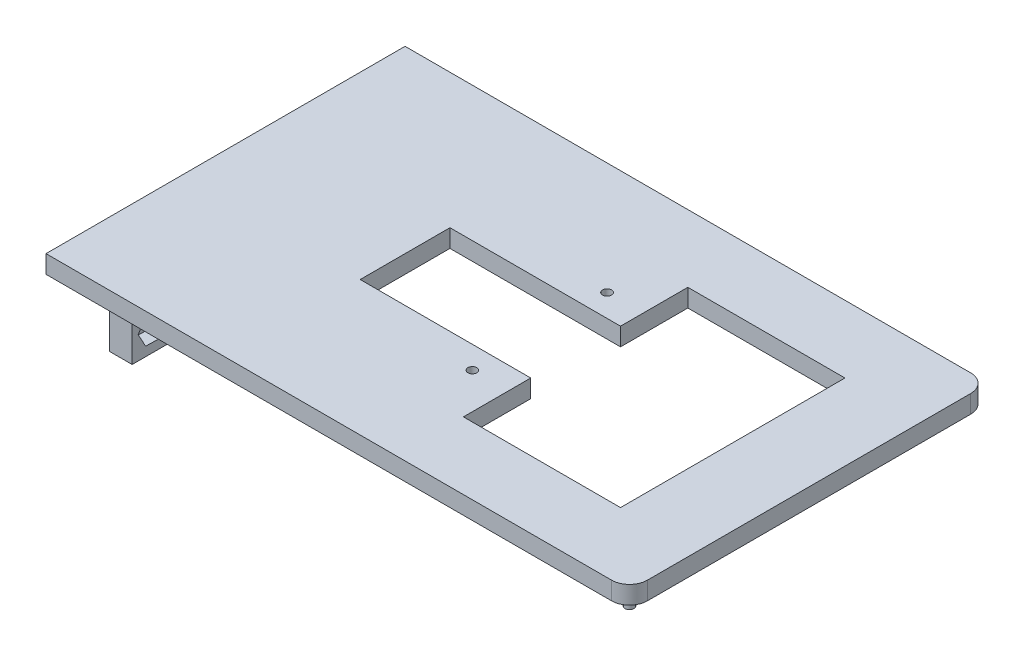
SolidWorks part; units mm, degrees
ref_plane "Front Plane" through (0, 0, 0) normal (0, 0, 1) x (1, 0, 0)
ref_plane "Top Plane" through (0, 0, 0) normal (0, 1, 0) x (1, 0, 0)
ref_plane "Right Plane" through (0, 0, 0) normal (1, 0, 0) x (0, 0, -1)
sketch "Sketch1" plane through (0, 0, 0) normal (0, 1, 0) x (1, 0, 0)
  line L1 (0, 0) -> (130, 0)
  line L2 (0, 0) -> (0, 80)
  line L3 (0, 80) -> (130, 80)
  line L4 (130, 0) -> (130, 80)
  arc A0 (126, 80) -> (130, 76) centre (126, 76) cw
  arc A1 (130, 4) -> (126, 0) centre (126, 4) cw
  point P5 (126, 4)
  point P6 (126, 76)
  dimension "D7" = 4
  dimension "D8" = 4
  dimension "D1" = 80
  dimension "D2" = 130
  dimension "D3" = 4
  dimension "D4" = 4
  dimension "D5" = 4
  dimension "D6" = 4
extrude "Boss-Extrude1" add sketch "Sketch1" along normal blind 4 contours A1 L4 A0 L3 L2 L1 region at (64.9576, 0, -40)
sketch "Sketch2" plane through (0, 0, 0) normal (0, -1, 0) x (-1, 0, 0)
  line L0 (-130, 4) -> (-130, 76) construction
  line L1 (0, 80) -> (-126, 80) construction
  circle A0 centre (-125.5, 4.5) radius 1
  circle A1 centre (-125.5, 75.5) radius 1
  point P0 (-125.5, 4.5)
  dimension "D3" = 2
  dimension "D6" = 2
  dimension "D1" = 4.5
  dimension "D2" = 4.5
  dimension "D4" = 4.5
  dimension "D5" = 4.5
extrude "Boss-Extrude2" add sketch "Sketch2" along normal blind 3.5
sketch "Sketch3" plane through (0, 0, 0) normal (0, -1, 0) x (-1, 0, 0)
  line L0 (0, 0) -> (0, 80) construction
  line L1 (0, 0) -> (-126, 0) construction
  line L2 (0, 80) -> (-126, 80) construction
  line L4 (-12, 2.2) -> (-17, 2.2)
  line L5 (-12, 2.2) -> (-12, 12.2)
  line L6 (-12, 12.2) -> (-17, 12.2)
  line L7 (-17, 2.2) -> (-17, 12.2)
  line L8 (-12, 77.8) -> (-17, 77.8)
  line L9 (-12, 77.8) -> (-12, 67.8)
  line L10 (-12, 67.8) -> (-17, 67.8)
  line L11 (-17, 77.8) -> (-17, 67.8)
  point P0 (-12, 2.2)
  point P1 (-12, 77.8)
  dimension "D1" = 12
  dimension "D2" = 2.2
  dimension "D3" = 2.2
  dimension "D4" = 12
  dimension "D5" = 10
  dimension "D6" = 5
  dimension "D7" = 10
  dimension "D8" = 5
extrude "Boss-Extrude3" add sketch "Sketch3" along normal blind 10
sketch "Sketch4" plane through (17, 0, 0) normal (1, 0, 0) x (0, 0, -1)
  line L0 (12.2, -10) -> (2.2, -10) construction
  line L1 (8.6657, -8.0383) -> (10.4641, -5.0766)
  line L2 (10.4641, -5.0766) -> (8.7984, -2.0383)
  line L3 (8.7984, -2.0383) -> (5.3343, -1.9617)
  line L4 (5.3343, -1.9617) -> (3.5359, -4.9234)
  line L5 (3.5359, -4.9234) -> (5.2016, -7.9617)
  line L6 (5.2016, -7.9617) -> (8.6657, -8.0383)
  line L7 (12.2, -10) -> (12.2, 0) construction
  circle A0 centre (7, -5) radius 3.0007 construction
  circle A1 centre (7, -5) radius 1.55
  dimension "D5" = 3.1
  dimension "D1" = 5
  dimension "D2" = 5.2
  dimension "D3" = 6
  dimension "D4" = 6.0015
extrude "Cut-Extrude1" cut sketch "Sketch4" against normal blind 3 contours L5 L6 L1 L2 L3 L4 A1 region at (17, -7.9079, -6.9357)
sketch "Sketch5" plane through (17, 0, 0) normal (1, 0, 0) x (0, 0, -1)
extrude "Cut-Extrude2" cut sketch "Sketch4<3>" against normal up to surface (5 mm away) contours A1 region at (17, -5, -7) up to face at (12, -5, -7.2)
sketch "Sketch4<3>" plane through (17, 0, 0) normal (1, 0, 0) x (0, 0, -1) same geometry as "Sketch4"
sketch "Sketch6" plane through (17, 0, 0) normal (1, 0, 0) x (0, 0, -1)
  line L0 (77.8, -10) -> (67.8, -10) construction
  line L1 (71.2679, -2) -> (69.5359, -5)
  line L2 (69.5359, -5) -> (71.2679, -8)
  line L3 (71.2679, -8) -> (74.7321, -8)
  line L4 (74.7321, -8) -> (76.4641, -5)
  line L5 (76.4641, -5) -> (74.7321, -2)
  line L6 (74.7321, -2) -> (71.2679, -2)
  line L7 (67.8, -10) -> (67.8, 0) construction
  circle A0 centre (73, -5) radius 3 construction
  circle A1 centre (73, -5) radius 1.55
  dimension "D5" = 3.1
  dimension "D1" = 6
  dimension "D2" = 6
  dimension "D3" = 5
  dimension "D4" = 5.2
sketch "Sketch7" plane through (0, 0, 0) normal (0, -1, 0) x (1, 0, 0)
  line L0 (0, 0) -> (126, 0) construction
  line L1 (0, 0) -> (0, -80) construction
  circle A0 centre (70, -25) radius 3
  circle A1 centre (70, -55) radius 3
  dimension "D3" = 6
  dimension "D4" = 6
  dimension "D1" = 30
  dimension "D2" = 25
  dimension "D5" = 70
  dimension "D6" = 70
extrude "Cut-Extrude3" cut sketch "Sketch7" against normal blind 2
sketch "Sketch8" plane through (0, 2, 0) normal (0, -1, 0) x (-1, 0, 0)
  line L0 (0, 80) -> (-126, 80) construction
  line L1 (0, 0) -> (0, 80) construction
  circle A0 centre (-70, 55) radius 1
  dimension "D1" = 2
  dimension "D2" = 25
  dimension "D3" = 70
extrude "Cut-Extrude4" cut sketch "Sketch8" against normal blind 2
sketch "Sketch9" plane through (0, 2, 0) normal (0, -1, 0) x (-1, 0, 0)
  line L0 (0, 0) -> (-126, 0) construction
  line L1 (0, 0) -> (0, 80) construction
  circle A0 centre (-70, 25) radius 1
  dimension "D1" = 2
  dimension "D2" = 25
  dimension "D3" = 70
extrude "Cut-Extrude5" cut sketch "Sketch9" against normal blind 2
sketch "Sketch10" plane through (0, 0, 0) normal (0, -1, 0) x (-1, 0, 0)
  line L0 (0, 0) -> (-126, 0) construction
  line L1 (-78, 30) -> (-40, 30)
  line L2 (0, 0) -> (0, 80) construction
  line L3 (-78, 50) -> (-40, 50)
  line L4 (-40, 30) -> (-40, 50)
  line L5 (-130, 4) -> (-130, 76) construction
  line L6 (-78, 30) -> (-78, 15)
  line L7 (-78, 15) -> (-113, 15)
  line L8 (-113, 15) -> (-113, 65)
  line L9 (-113, 65) -> (-78, 65)
  line L10 (-78, 65) -> (-78, 50)
  dimension "D1" = 20
  dimension "D2" = 40
  dimension "D3" = 30
  dimension "D4" = 52
  dimension "D5" = 15
  dimension "D6" = 15
  dimension "D7" = 35
  dimension "D8" = 17
extrude "Cut-Extrude6" cut sketch "Sketch10" against normal blind 4
extrude "Cut-Extrude7" cut sketch "Sketch6" against normal blind 3 contours L5 L6 L1 L2 L3 L4 A1 region at (17, -2.0917, -73)
extrude "Cut-Extrude8" cut sketch "Sketch6<3>" against normal up to surface (5 mm away) contours A1 region at (17, -5, -73) up to face at (12, -5, -72.8)
sketch "Sketch6<3>" plane through (17, 0, 0) normal (1, 0, 0) x (0, 0, -1) same geometry as "Sketch6"
